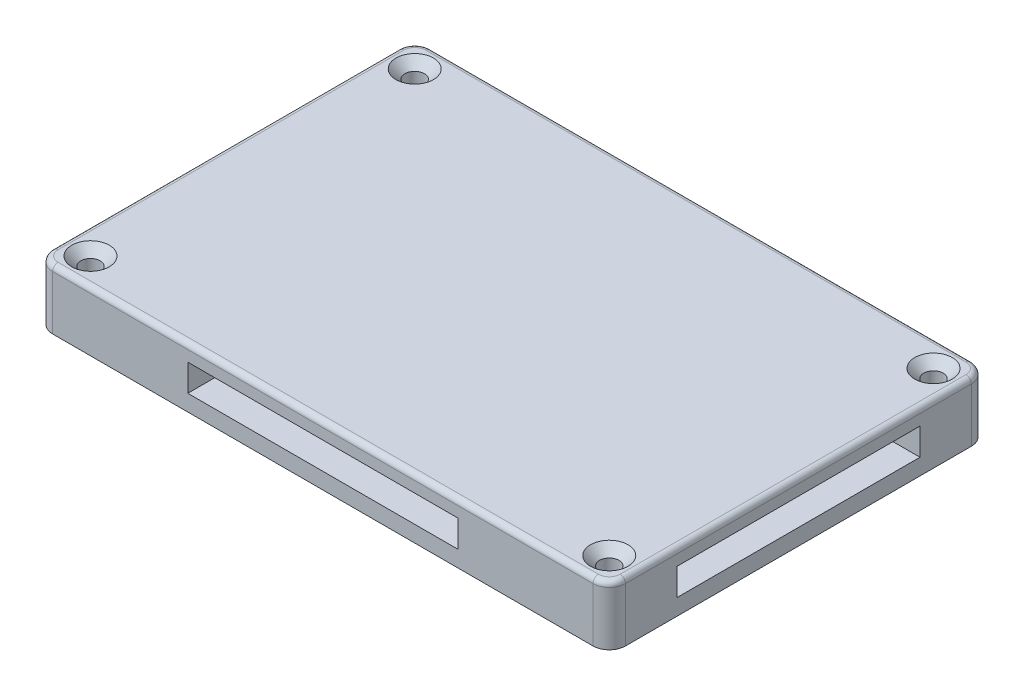
SolidWorks part; units mm, degrees
ref_plane "Alzado" through (0, 0, 0) normal (0, 0, 1) x (1, 0, 0)
ref_plane "Planta" through (0, 0, 0) normal (0, 1, 0) x (1, 0, 0)
ref_plane "Vista lateral" through (0, 0, 0) normal (1, 0, 0) x (0, 0, -1)
sketch "Croquis1" plane through (0, 0, 0) normal (0, 1, 0) x (1, 0, 0)
  line L1 (0, 0) -> (106, 0)
  line L2 (0, 0) -> (0, 70)
  line L3 (0, 70) -> (106, 70)
  line L4 (106, 0) -> (106, 70)
  dimension "D1" = 106
  dimension "D2" = 70
extrude "Saliente-Extruir1" add sketch "Croquis1" along normal blind 11
sketch "Croquis2" plane through (0, 0, 0) normal (0, 0, 1) x (1, 0, 0)
  line L0 (0, 0) -> (0, 3) construction
  line L1 (0, 11) -> (0, 0) construction
  line L2 (0, 3) -> (28, 3) construction
  line L4 (28, 3) -> (78, 3)
  line L5 (28, 3) -> (28, 8)
  line L6 (28, 8) -> (78, 8)
  line L7 (78, 3) -> (78, 8)
  dimension "D1" = 3
  dimension "D2" = 28
  dimension "D3" = 50
  dimension "D4" = 5
extrude "Cortar-Extruir1" cut sketch "Croquis2" against normal through all
sketch "Croquis3" plane through (106, 0, 0) normal (1, 0, 0) x (0, 0, -1)
  line L0 (0, 0) -> (0, 3) construction
  line L1 (0, 3) -> (12.5, 3) construction
  line L3 (12.5, 3) -> (57.5, 3)
  line L4 (12.5, 3) -> (12.5, 8)
  line L5 (12.5, 8) -> (57.5, 8)
  line L6 (57.5, 3) -> (57.5, 8)
  dimension "D1" = 45
  dimension "D2" = 12.5
  dimension "D3" = 5
extrude "Cortar-Extruir2" cut sketch "Croquis3" against normal through all
fillet "Redondeo1" radius 3 4 edges at (0, 5.5, 0) (0, 5.5, -70) (106, 5.5, -70) (106, 5.5, 0)
sketch "Croquis5" plane through (0, 11, 0) normal (0, 1, 0) x (1, 0, 0)
  line L0 (5, 0) -> (5, 5) construction
  line L1 (3, 0) -> (103, 0) construction
  line L2 (5, 5) -> (0, 5) construction
  line L3 (0, 67) -> (0, 3) construction
  line L4 (53, 0) -> (53, 70) construction
  line L5 (103, 70) -> (3, 70) construction
  line L6 (0, 35) -> (106, 35) construction
  line L7 (106, 3) -> (106, 67) construction
  point P15 (101, 5)
  point P16 (5, 5)
  point P17 (101, 65)
  point P18 (5, 65)
  dimension "D1" = 5
  dimension "D2" = 5
hole_wizard "Avellanado para tornillo con cabeza avellanada de clavija hexagonal de M32" positions "Croquis11" profile "Croquis12" countersink size "M3" standard "DIN" end condition through all
sketch "Croquis11" plane through (0, 11, 0) normal (0, 1, 0) x (1, 0, 0)
  point P0 (5, 65)
  point P3 (101, 65)
  point P6 (101, 5)
  point P9 (5, 5)
sketch "Croquis12" plane through (5, 11, -65) normal (1, 0, 0) x (0, 0, 1)
  line L0 (0, 0) -> (0, 11)
  line L1 (0, 11) -> (1.8, 11)
  line L2 (1.8, 11) -> (1.8, 1.67)
  line L3 (1.8, 1.67) -> (3.47, 0)
  line L5 (3.47, 0) -> (0, 0)
  line L6 (-1.8, 1.67) -> (-3.47, 0) construction
  line L11 (0, -6.35) -> (0, 107.95) construction
  dimension "Diámetro de taladro hasta el siguiente" = 3.6
  dimension "Profundidad de taladro hasta el siguiente" = 11
  dimension "Diámetro de avellanado cercano" = 6.94
  dimension "Ángulo de avellanado cercano" = 90
fillet "Redondeo2" radius 1 8 edges at (105.1213, 11, -0.8787) (53, 11, 0) (0.8787, 11, -0.8787) (0, 11, -35) (0.8787, 11, -69.1213) (53, 11, -70) (105.1213, 11, -69.1213) (106, 11, -35)
